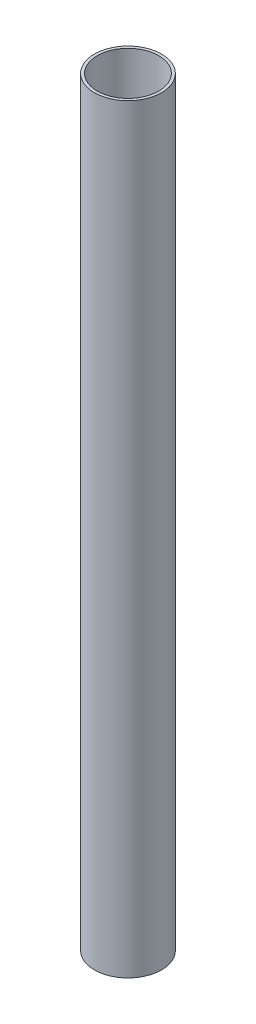
SolidWorks part; units mm, degrees
material "6061 Alloy"
ref_plane "Front Plane" through (0, 0, 0) normal (0, 0, 1) x (1, 0, 0)
ref_plane "Top Plane" through (0, 0, 0) normal (0, 1, 0) x (1, 0, 0)
ref_plane "Right Plane" through (0, 0, 0) normal (1, 0, 0) x (0, 0, -1)
sketch "Sketch2" plane through (0, 0, 0) normal (0, 1, 0) x (1, 0, 0)
  circle A0 centre (0, 0) radius 19.05
  circle A1 centre (0, 0) radius 17.4625
  dimension "D1" = 38.1
  dimension "D2" = 1.5875
extrude "Boss-Extrude1" add sketch "Sketch2" along normal blind 431.8
